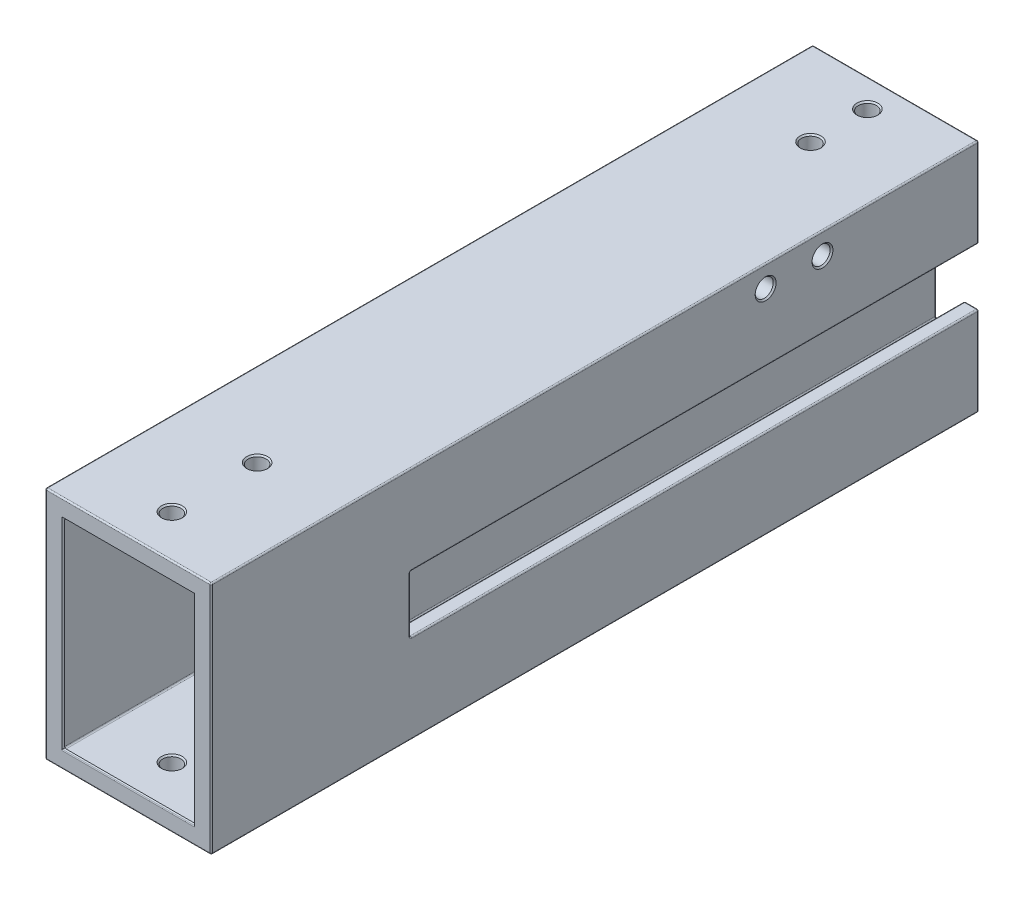
SolidWorks part; units mm, degrees
ref_plane "Front Plane" through (0, 0, 0) normal (0, 0, 1) x (1, 0, 0)
ref_plane "Top Plane" through (0, 0, 0) normal (0, 1, 0) x (1, 0, 0)
ref_plane "Right Plane" through (0, 0, 0) normal (1, 0, 0) x (0, 0, -1)
sketch "Sketch1" plane through (0, 0, 0) normal (0, 0, 1) x (1, 0, 0)
  line L0 (-6.35, -6.35) -> (-6.35, 76.35)
  line L1 (0, 0) -> (45.72, 0) construction
  line L2 (0, 0) -> (0, 70) construction
  line L3 (0, 70) -> (45.72, 70) construction
  line L4 (45.72, 0) -> (45.72, 70) construction
  line L5 (-6.35, 76.35) -> (52.07, 76.35)
  line L6 (52.07, -6.35) -> (52.07, 76.35)
  line L7 (-6.35, -6.35) -> (52.07, -6.35)
  dimension "D1" = 45.72
  dimension "D2" = 70
  dimension "D3" = 6.35
extrude "Boss-Extrude1" add sketch "Sketch1" against normal blind 270
sketch "Sketch2" plane through (0, 0, 0) normal (0, 0, 1) x (1, 0, 0)
  line L0 (45.72, 70) -> (0, 70)
  line L1 (0, 70) -> (0, 0)
  line L2 (0, 0) -> (45.72, 0)
  line L3 (45.72, 0) -> (45.72, 70)
  line L4 (-6.35, -6.35) -> (52.07, -6.35)
  line L5 (52.07, -6.35) -> (52.07, 76.35)
  line L6 (52.07, 76.35) -> (-6.35, 76.35)
  line L7 (-6.35, 76.35) -> (-6.35, -6.35)
  line L8 (-6.35, -6.35) -> (52.07, -6.35) construction
  line L9 (52.07, -6.35) -> (52.07, 76.35) construction
  line L10 (52.07, 76.35) -> (-6.35, 76.35) construction
  line L11 (-6.35, 76.35) -> (-6.35, -6.35) construction
  dimension "D1" = 0
  dimension "D2" = 6.35
extrude "Cut-Extrude1" cut sketch "Sketch2" against normal blind 60
sketch "Sketch3" plane through (0, -6.35, 0) normal (0, -1, 0) x (1, 0, 0)
  circle A1 centre (22.86, -240) radius 3.175
  circle A3 centre (23.22, -45) radius 3.175
  circle A4 centre (23.22, -45) radius 3.175
  circle A5 centre (23.22, -15) radius 3.175
  circle A6 centre (23.22, -15) radius 3.175
  circle A7 centre (22.86, -240) radius 3.175
  circle A8 centre (22.86, -260) radius 3.175
  circle A9 centre (22.86, -260) radius 3.175
  dimension "D1" = 0
  dimension "D2" = 0
  dimension "D3" = 0
  dimension "D4" = 0
extrude "Cut-Extrude2" cut sketch "Sketch3" against normal through all
sketch "Sketch8" plane through (0, 0, -270) normal (0, 0, -1) x (-1, 0, 0)
  line L0 (6.35, 35) -> (-52.07, 35) construction
  line L1 (6.35, 25) -> (1.35, 25)
  line L2 (1.35, 25) -> (1.35, 15)
  line L3 (1.35, 15) -> (-8.65, 15)
  line L4 (-52.07, -6.35) -> (6.35, -6.35)
  line L5 (6.35, -6.35) -> (6.35, 76.35)
  line L6 (6.35, 76.35) -> (-52.07, 76.35)
  line L7 (-52.07, 76.35) -> (-52.07, -6.35)
  line L8 (-52.07, -6.35) -> (6.35, -6.35) construction
  line L9 (6.35, -6.35) -> (6.35, 76.35) construction
  line L10 (6.35, 76.35) -> (-52.07, 76.35) construction
  line L11 (-52.07, 76.35) -> (-52.07, -6.35) construction
  line L12 (-8.65, 15) -> (-8.65, 55)
  line L13 (6.35, 45) -> (1.35, 45)
  line L14 (1.35, 45) -> (1.35, 55)
  line L15 (1.35, 55) -> (-8.65, 55)
  line L16 (-22.86, -6.35) -> (-22.86, 76.35) construction
  line L17 (-52.07, 25) -> (-47.07, 25)
  line L18 (-47.07, 25) -> (-47.07, 15)
  line L19 (-47.07, 15) -> (-37.07, 15)
  line L20 (-52.07, 45) -> (-47.07, 45)
  line L21 (-47.07, 55) -> (-37.07, 55)
  line L22 (-47.07, 45) -> (-47.07, 55)
  line L23 (-37.07, 15) -> (-37.07, 55)
  line L24 (6.35, 45) -> (6.35, 25)
  line L25 (-52.07, 45) -> (-52.07, 25)
  point P2 (6.35, 35)
  point P16 (-8.65, 35)
  dimension "D2" = 10
  dimension "D3" = 20
  dimension "D4" = 10
  dimension "D5" = 5
  dimension "D1" = 0
extrude "Cut-Extrude4" cut sketch "Sketch8" against normal blind 200
sketch "Sketch11" plane through (-6.35, 0, 0) normal (-1, 0, 0) x (0, 0, 1)
  circle A0 centre (-195, 68.7312) radius 3.175 construction
  circle A1 centre (-215, 68.7312) radius 3.175 construction
  circle A2 centre (-195, 68.7312) radius 3.175
  circle A3 centre (-215, 68.7312) radius 3.175
extrude "Cut-Extrude5" cut sketch "Sketch11" against normal through all
sketch "Sketch12" plane through (0, 0, -270) normal (0, 0, -1) x (-1, 0, 0)
  line L0 (-52.07, 45) -> (-52.07, 25) construction
  line L1 (-12.86, 10) -> (-32.86, 10)
  line L2 (-12.86, 10) -> (-12.86, 60)
  line L3 (-12.86, 60) -> (-32.86, 60)
  line L4 (-32.86, 10) -> (-32.86, 60)
  line L20 (6.35, -6.35) -> (6.35, 25)
  line L21 (6.35, 25) -> (1.35, 25)
  line L22 (1.35, 25) -> (1.35, 15)
  line L23 (1.35, 15) -> (-8.65, 15)
  line L24 (-8.65, 15) -> (-8.65, 55)
  line L25 (-8.65, 55) -> (1.35, 55)
  line L26 (1.35, 55) -> (1.35, 45)
  line L27 (1.35, 45) -> (6.35, 45)
  line L28 (6.35, 45) -> (6.35, 76.35)
  line L29 (6.35, 76.35) -> (-52.07, 76.35)
  line L30 (-52.07, 76.35) -> (-52.07, 45)
  line L31 (-52.07, 45) -> (-47.07, 45)
  line L32 (-47.07, 45) -> (-47.07, 55)
  line L33 (-47.07, 55) -> (-37.07, 55)
  line L34 (-37.07, 55) -> (-37.07, 15)
  line L35 (-37.07, 15) -> (-47.07, 15)
  line L36 (-47.07, 15) -> (-47.07, 25)
  line L37 (-47.07, 25) -> (-52.07, 25)
  line L38 (-52.07, 25) -> (-52.07, -6.35)
  line L39 (-52.07, -6.35) -> (6.35, -6.35)
  line L40 (6.35, -6.35) -> (6.35, 25) construction
  line L41 (6.35, 25) -> (1.35, 25) construction
  line L42 (1.35, 25) -> (1.35, 15) construction
  line L43 (1.35, 15) -> (-8.65, 15) construction
  line L44 (-8.65, 15) -> (-8.65, 55) construction
  line L45 (-8.65, 55) -> (1.35, 55) construction
  line L46 (1.35, 55) -> (1.35, 45) construction
  line L47 (1.35, 45) -> (6.35, 45) construction
  line L48 (6.35, 45) -> (6.35, 76.35) construction
  line L49 (6.35, 76.35) -> (-52.07, 76.35) construction
  line L50 (-52.07, 76.35) -> (-52.07, 45) construction
  line L51 (-52.07, 45) -> (-47.07, 45) construction
  line L52 (-47.07, 45) -> (-47.07, 55) construction
  line L53 (-47.07, 55) -> (-37.07, 55) construction
  line L54 (-37.07, 55) -> (-37.07, 15) construction
  line L55 (-37.07, 15) -> (-47.07, 15) construction
  line L56 (-47.07, 15) -> (-47.07, 25) construction
  line L57 (-47.07, 25) -> (-52.07, 25) construction
  line L58 (-52.07, 25) -> (-52.07, -6.35) construction
  line L59 (-52.07, -6.35) -> (6.35, -6.35) construction
  point P10 (-32.86, 35)
  point P12 (-22.86, 10)
  point P14 (-52.07, 35)
  point P16 (-22.86, -6.35)
  dimension "D2" = 50
  dimension "D3" = 20
  dimension "D1" = 0
extrude "Cut-Extrude6" cut sketch "Sketch12" against normal blind 50
chamfer "Chamfer1" distance 0.5 angle 45 20 edges at (-6.35, 68.7312, -211.825) (52.07, 68.7312, -211.825) (-6.35, 68.7312, -191.825) (52.07, 68.7312, -191.825) (23.22, 0, -18.175) (23.22, -6.35, -18.175) (23.22, 0, -48.175) (23.22, -6.35, -48.175) (23.22, 76.35, -18.175) (23.22, 70, -11.825) (23.22, 76.35, -48.175) (23.22, 70, -41.825) (22.86, -6.35, -243.175) (26.035, 10, -240) (22.86, -6.35, -263.175) (26.035, 10, -260) (22.86, 76.35, -243.175) (19.685, 60, -240) (22.86, 76.35, -263.175) (19.685, 60, -260)
chamfer "Chamfer2" distance 0.5 angle 45 8 edges at (0, 35, 0) (22.86, 70, 0) (22.86, 0, 0) (45.72, 35, 0) (22.86, 60, -270) (32.86, 35, -270) (12.86, 35, -270) (22.86, 10, -270)
fillet "Fillet1" radius 0.5 77 edges at (22.86, 0, -60) (0, 35, -60) (22.86, 70, -60) (45.72, 35, -60) (52.07, 45, -170) (49.57, 45, -270) (47.07, 45, -170) (47.07, 50, -270) (47.07, 55, -170) (42.07, 55, -270) (47.07, 20, -270) (47.07, 15, -170) (42.07, 15, -270) (52.07, 25, -170) (47.07, 25, -170) (49.57, 25, -270) (37.07, 15, -170) (37.07, 55, -170) (37.07, 35, -270) (49.57, 45, -70) (47.07, 50, -70) (42.07, 55, -70) (37.07, 35, -70) (42.07, 15, -70) (47.07, 20, -70) (49.57, 25, -70) (52.07, 35, -70) (22.86, 10, -220) (32.86, 35, -220) (22.86, 60, -220) (12.86, 35, -220) (-1.35, 55, -170) (3.65, 55, -270) (-1.35, 20, -270) (-1.35, 15, -170) (3.65, 15, -270) (8.65, 55, -170) (8.65, 15, -170) (8.65, 35, -270) (-6.35, 45, -170) (-1.35, 45, -170) (-3.85, 45, -270) (-1.35, 25, -170) (-6.35, 25, -170) (-3.85, 25, -270) (-3.85, 25, -70) (-1.35, 20, -70) (3.65, 15, -70) (8.65, 35, -70) (3.65, 55, -70) (-1.35, 50, -70) (-3.85, 45, -70) (-6.35, 35, -70) (52.07, 76.35, -135) (-6.35, 76.35, -135) (-6.35, -6.35, -135) (52.07, -6.35, -135) (0, 70, -30.25) (45.72, 70, -30.25) (45.72, 0, -30.25) (0, 0, -30.25) (22.86, 76.35, 0) (52.07, 35, 0) (22.86, -6.35, 0) (-6.35, 35, 0) (52.07, 9.325, -270) (22.86, -6.35, -270) (-6.35, 9.325, -270) (52.07, 60.675, -270) (-1.35, 50, -270) (-6.35, 60.675, -270) (22.86, 76.35, -270) (22.86, -0.5, 0) (32.86, 10, -244.75) (12.86, 10, -244.75) (32.86, 60, -244.75) (12.86, 60, -244.75)
